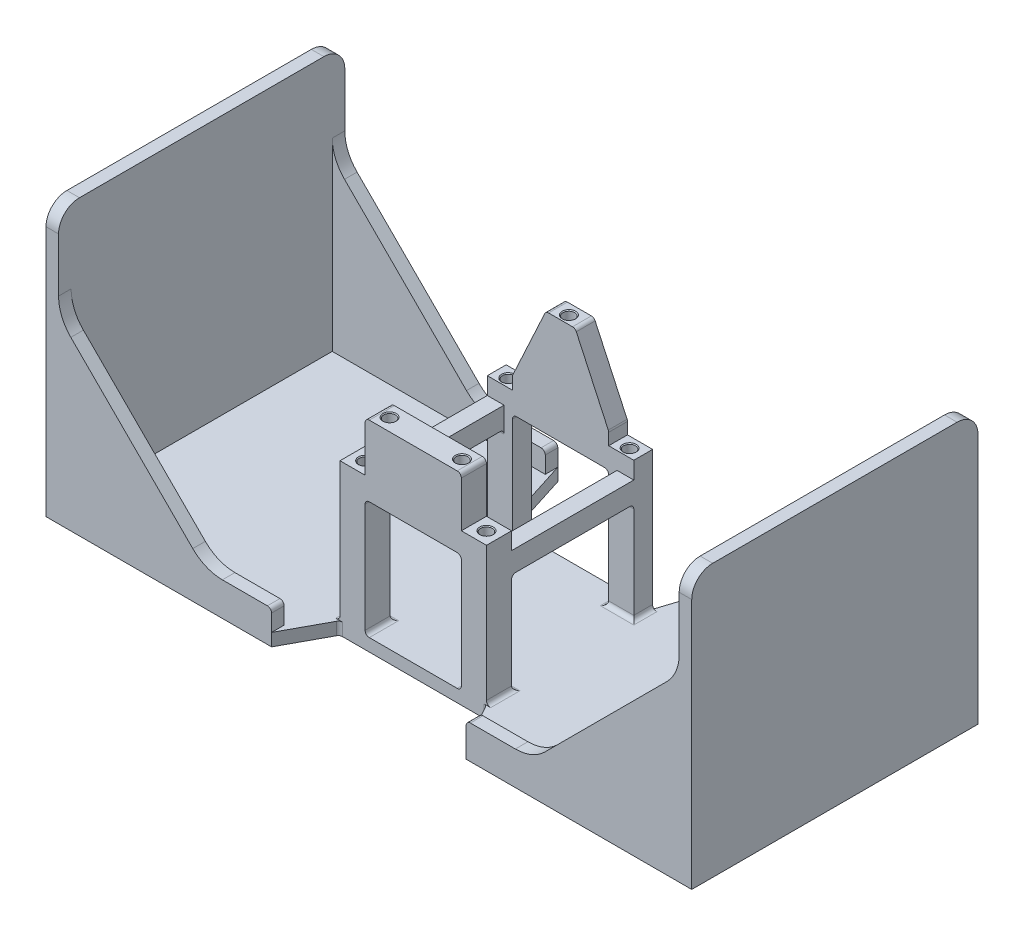
SolidWorks part; units mm, degrees
ref_plane "Front Plane" through (0, 0, 0) normal (0, 0, 1) x (1, 0, 0)
ref_plane "Top Plane" through (0, 0, 0) normal (0, 1, 0) x (1, 0, 0)
ref_plane "Right Plane" through (0, 0, 0) normal (1, 0, 0) x (0, 0, -1)
sketch "Sketch1" plane through (0, 0, 0) normal (0, 1, 0) x (1, 0, 0)
  line L1 (77.15, -34.2) -> (-77.15, -34.2)
  line L2 (77.15, -34.2) -> (77.15, 34.2)
  line L3 (77.15, 34.2) -> (-77.15, 34.2)
  line L4 (-77.15, -34.2) -> (-77.15, 34.2)
  line L5 (77.15, -34.2) -> (-77.15, 34.2) construction
  line L6 (77.15, 34.2) -> (-77.15, -34.2) construction
  point P0 (0, 0)
  dimension "D1" = 154.3
  dimension "D2" = 68.4
extrude "Boss-Extrude1" add sketch "Sketch1" along normal blind 3
sketch "Sketch2" plane through (0, 3, 0) normal (0, 1, 0) x (1, 0, 0)
  line L0 (0, 0) -> (0, -20.6) construction
  line L1 (8.65, -20.6) -> (-8.65, -20.6) construction
  line L2 (0, 0) -> (0, 13.6) construction
  line L3 (-11.5, 11.6) -> (-11.5, 16.1)
  line L8 (-11.5, -23.6) -> (11.5, -23.6)
  line L9 (-11.5, -23.6) -> (-11.5, -17.6)
  line L10 (-11.5, 16.1) -> (11.5, 16.1)
  line L11 (11.5, -23.6) -> (11.5, -17.6)
  line L12 (-11.5, -17.6) -> (11.5, -17.6)
  line L14 (-11.5, 11.6) -> (11.5, 11.6)
  line L16 (11.5, 11.6) -> (11.5, 16.1)
  line L17 (-11.5, -23.6) -> (-17.5, -23.6)
  line L18 (11.5, 16.1) -> (17.5, 16.1)
  line L19 (11.5, 16.1) -> (11.5, -23.6)
  line L20 (11.5, -23.6) -> (17.5, -23.6)
  line L21 (17.5, 16.1) -> (17.5, -23.6)
  line L22 (-17.5, 16.1) -> (-17.5, -23.6)
  line L23 (-11.5, 16.1) -> (-17.5, 16.1)
  line L24 (-11.5, 16.1) -> (-11.5, -23.6)
  circle A0 centre (-8.65, -20.6) radius 1.4
  circle A1 centre (8.65, -20.6) radius 1.4
  circle A2 centre (0, 13.6) radius 1.4
  point P5 (0, -20.6)
  point P14 (0, 16.1)
  point P15 (0, 11.6)
  point P28 (-11.5, -20.6)
  dimension "D3" = 2.8
  dimension "D4" = 2.8
  dimension "D6" = 2.8
  dimension "D1" = 20.6
  dimension "D2" = 17.3
  dimension "D5" = 13.6
  dimension "D7" = 23
  dimension "D8" = 6
  dimension "D9" = 2.5
  dimension "D10" = 6
  dimension "D12" = 2
extrude "Boss-Extrude2" add sketch "Sketch2" along normal blind 45 contours L14 L16 L10 L3 A2 | L12 L9 L8 L11 A1 A0 region at (-11.2656, 3, -13.85) region at (0, 3, 20.6)
extrude "Boss-Extrude3" add sketch "Sketch2<3>" along normal blind 8.4 from surface contours L14 L16 L10 L3 A2 region at (-11.2656, 3, -13.85) starting at face at (0, 48, -12.2)
sketch "Sketch2<3>" plane through (0, 3, 0) normal (0, 1, 0) x (1, 0, 0) same geometry as "Sketch2"
extrude "Boss-Extrude4" add sketch "Sketch2<5>" along normal blind 29 contours L24 L3 L23 L22 L17 L9 | L21 L18 L16 L19 L11 L20 region at (-14.5, 3, 3.75) region at (14.5, 3, 3.75)
sketch "Sketch2<5>" plane through (0, 3, 0) normal (0, 1, 0) x (1, 0, 0) same geometry as "Sketch2"
sketch "Sketch3" plane through (0, 32, 0) normal (0, 1, 0) x (1, 0, 0)
  line L0 (11.5, -17.6) -> (11.5, 11.6) construction
  line L1 (11.5, 11.6) -> (13.5, 11.6)
  line L2 (11.5, 11.6) -> (11.5, -17.6)
  line L3 (11.5, -17.6) -> (13.5, -17.6)
  line L4 (13.5, 11.6) -> (13.5, -17.6)
  line L6 (0, 16.1) -> (0, -23.6) construction
  line L7 (-17.5, 16.1) -> (17.5, 16.1) construction
  line L8 (-11.5, -23.6) -> (11.5, -23.6) construction
  line L9 (-11.5, -17.6) -> (-13.5, -17.6)
  line L10 (-13.5, 11.6) -> (-13.5, -17.6)
  line L11 (-11.5, 11.6) -> (-13.5, 11.6)
  line L12 (-11.5, 11.6) -> (-11.5, -17.6)
  line L14 (11.5, 11.6) -> (-11.5, 11.6) construction
  line L15 (-11.5, -17.6) -> (11.5, -17.6) construction
  dimension "D3" = 2
extrude "Cut-Extrude1" cut sketch "Sketch3" against normal up to surface (29 mm away) up to face at (0, 3, 3)
sketch "Sketch4" plane through (0, 3, 0) normal (0, 1, 0) x (1, 0, 0)
  line L0 (-77.15, -34.2) -> (77.15, -34.2) construction
  line L1 (77.15, 34.2) -> (74.15, 34.2)
  line L2 (77.15, 34.2) -> (77.15, -34.2)
  line L3 (77.15, -34.2) -> (74.15, -34.2)
  line L4 (74.15, 34.2) -> (74.15, -34.2)
  line L5 (0, -34.2) -> (0, 34.2) construction
  line L6 (-77.15, 34.2) -> (-74.15, 34.2)
  line L7 (-77.15, 34.2) -> (-77.15, -34.2)
  line L8 (-77.15, -34.2) -> (-74.15, -34.2)
  line L9 (-74.15, 34.2) -> (-74.15, -34.2)
  line L10 (74.15, 34.2) -> (23.25, 34.2)
  line L11 (74.15, 34.2) -> (74.15, 31.2)
  line L12 (74.15, 31.2) -> (23.25, 31.2)
  line L13 (23.25, 34.2) -> (23.25, 31.2)
  line L14 (77.15, 34.2) -> (-77.15, 34.2) construction
  line L15 (77.15, 0) -> (-75.15, 0) construction
  line L16 (74.15, -31.2) -> (23.25, -31.2)
  line L17 (23.25, -34.2) -> (23.25, -31.2)
  line L18 (74.15, -34.2) -> (23.25, -34.2)
  line L19 (74.15, -34.2) -> (74.15, -31.2)
  line L20 (-74.15, -31.2) -> (-23.25, -31.2)
  line L21 (-74.15, 34.2) -> (-23.25, 34.2)
  line L22 (-74.15, 34.2) -> (-74.15, 31.2)
  line L23 (-74.15, 31.2) -> (-23.25, 31.2)
  line L24 (-23.25, 34.2) -> (-23.25, 31.2)
  line L25 (-23.25, -34.2) -> (-23.25, -31.2)
  line L26 (-74.15, -34.2) -> (-23.25, -34.2)
  line L27 (-74.15, -34.2) -> (-74.15, -31.2)
  line M7 (-77.15, 34.2) -> (-77.15, -34.2)
  line M8 (-77.15, -34.2) -> (77.15, -34.2)
  line M9 (77.15, -34.2) -> (77.15, 34.2)
  line M10 (77.15, 34.2) -> (-77.15, 34.2)
  dimension "D1" = 3
  dimension "D2" = 3
  dimension "D3" = 3
  dimension "D4" = 50.9
  dimension "D5" = 50.9
  dimension "D6" = 3
extrude "Boss-Extrude5" add sketch "Sketch4" along normal blind 62 contours L4 M10 M8 M9 | L9 M10 M7 M8 region at (75.65, 3, 0) region at (-75.65, 3, 0)
extrude "Boss-Extrude6" add sketch "Sketch4<3>" along normal blind 5 contours L13 L12 L4 M10 | L17 L4 L16 M8 | L24 L9 L23 M10 | L27 L20 L25 L26 region at (48.7, 3, -32.7) region at (48.7, 3, 32.7) region at (-48.7, 3, -32.7)
sketch "Sketch4<3>" plane through (0, 3, 0) normal (0, 1, 0) x (1, 0, 0) same geometry as "Sketch4"
sketch "Sketch5" plane through (0, 3, 0) normal (0, 1, 0) x (1, 0, 0)
  line L0 (23.25, -34.2) -> (17.5, -23.6)
  line L1 (17.5, -23.6) -> (-17.5, -23.6)
  line L2 (-17.5, -23.6) -> (-23.25, -34.2)
  line L3 (-23.25, -34.2) -> (23.25, -34.2)
  line L4 (17.5, 16.1) -> (23.25, 34.2)
  line L5 (23.25, 34.2) -> (-23.25, 34.2)
  line L6 (-23.25, 34.2) -> (-17.5, 16.1)
  line L7 (-17.5, 16.1) -> (17.5, 16.1)
extrude "Cut-Extrude2" cut sketch "Sketch5" against normal through all
fillet "Fillet1" radius 5 4 edges at (-75.65, 65, 34.2) (-75.65, 65, -34.2) (75.65, 65, 34.2) (75.65, 65, -34.2)
fillet "Fillet2" radius 1 8 edges at (-17.5, 1.5, 23.6) (17.5, 1.5, 23.6) (-17.5, 1.5, -16.1) (17.5, 1.5, -16.1) (23.25, 8, 32.7) (-23.25, 8, 32.7) (-23.25, 8, -32.7) (23.25, 8, -32.7)
sketch "Sketch6" plane through (0, 32, 0) normal (0, 1, 0) x (1, 0, 0)
  line L0 (-17.5, 16.1) -> (-17.5, -23.6) construction
  line L1 (-11.5, -23.6) -> (-17.5, -23.6)
  line L2 (-11.5, -23.6) -> (-11.5, -17.6)
  line L3 (-11.5, -17.6) -> (-17.5, -17.6)
  line L4 (-17.5, -23.6) -> (-17.5, -17.6)
  line L5 (17.5, 16.1) -> (17.5, -23.6) construction
  line L6 (11.5, -23.6) -> (17.5, -23.6)
  line L7 (11.5, -23.6) -> (11.5, -17.6)
  line L8 (11.5, -17.6) -> (17.5, -17.6)
  line L9 (17.5, -23.6) -> (17.5, -17.6)
  line L10 (17.5, 13.6) -> (-17.5, 13.6) construction
  line L15 (-17.5, 16.1) -> (-17.5, -23.6) construction
  line L16 (17.5, -17.6) -> (11.5, -23.6) construction
  line L21 (17.5, -23.6) -> (11.5, -17.6) construction
  line L22 (-11.5, -17.6) -> (-17.5, -23.6) construction
  line L23 (-11.5, -23.6) -> (-17.5, -17.6) construction
  line L26 (17.5, 16.1) -> (11.5, 16.1)
  line L27 (17.5, 16.1) -> (17.5, 11.6)
  line L28 (-13.5, -17.6) -> (13.5, -17.6) construction
  line L29 (17.5, 11.6) -> (11.5, 11.6)
  line L30 (11.5, 16.1) -> (11.5, 11.6)
  line L31 (-11.5, 16.1) -> (-17.5, 16.1)
  line L32 (-11.5, 16.1) -> (-11.5, 11.6)
  line L33 (-11.5, 11.6) -> (-17.5, 11.6)
  line L34 (-17.5, 16.1) -> (-17.5, 11.6)
  circle A0 centre (14.5, -20.6) radius 1.4
  circle A1 centre (-14.5, -20.6) radius 1.4
  circle A3 centre (14.5, 13.6) radius 1.4
  circle A4 centre (0, 13.6) radius 1.4 construction
  circle A5 centre (-14.5, 13.6) radius 1.4
  point P21 (0, 13.6)
  dimension "D1" = 2.8
  dimension "D2" = 2.8
  dimension "D3" = 2.8
  dimension "D4" = 2.8
extrude "Boss-Extrude7" add sketch "Sketch6" along normal blind 4.1
sketch "Sketch8" plane through (17.5, 0, 0) normal (1, 0, 0) x (0, 0, -1)
  line L0 (-17.6, 36.1) -> (-17.6, 32) construction
  line L1 (-17.6, 27) -> (11.6, 27)
  line L2 (-17.6, 27) -> (-17.6, 3)
  line L3 (-17.6, 3) -> (11.6, 3)
  line L4 (11.6, 27) -> (11.6, 3)
  line L6 (16.1, 3) -> (-23.6, 3) construction
  line L7 (11.6, 32) -> (-17.6, 32) construction
  line L8 (11.6, 36.1) -> (11.6, 32) construction
  dimension "D1" = 5
extrude "Cut-Extrude4" cut sketch "Sketch8" against normal blind 40
sketch "Sketch9" plane through (0, 0, 23.6) normal (0, 0, 1) x (1, 0, 0)
  line L0 (11.5, 48) -> (11.5, 36.1) construction
  line L1 (-11.5, 31.1) -> (11.5, 31.1)
  line L2 (-11.5, 31.1) -> (-11.5, 3)
  line L3 (-11.5, 3) -> (11.5, 3)
  line L4 (11.5, 31.1) -> (11.5, 3)
  line L5 (-11.5, 48) -> (-11.5, 36.1) construction
  line L6 (-17.5, 3) -> (17.5, 3) construction
  line L7 (17.5, 36.1) -> (11.5, 36.1) construction
  dimension "D1" = 5
extrude "Cut-Extrude5" cut sketch "Sketch9" against normal blind 40
sketch "Sketch10" plane through (0, 0, -16.1) normal (0, 0, -1) x (-1, 0, 0)
  line L0 (0, 56.4) -> (0, 31.1) construction
  line L1 (-11.5, 56.4) -> (11.5, 56.4) construction
  line L2 (11.5, 31.1) -> (-11.5, 31.1) construction
  line L3 (3.5, 56.4) -> (-3.5, 56.4)
  line L4 (-3.5, 56.4) -> (-11.5, 39.1)
  line L5 (-11.5, 56.4) -> (-11.5, 36.1) construction
  line L6 (-11.5, 39.1) -> (-11.5, 36.1)
  line L7 (-11.5, 36.1) -> (11.5, 36.1)
  line L8 (11.5, 36.1) -> (11.5, 39.1)
  line L9 (11.5, 56.4) -> (11.5, 36.1) construction
  line L10 (11.5, 39.1) -> (3.5, 56.4)
  line L11 (-17.5, 36.1) -> (-11.5, 36.1) construction
  line L12 (11.5, 36.1) -> (17.5, 36.1) construction
  line L13 (11.5, 56.4) -> (11.5, 36.1) construction
  point P11 (0, 56.4)
  line M16 (11.5, 36.1) -> (11.5, 56.4)
  line M17 (11.5, 56.4) -> (-11.5, 56.4)
  line M18 (-11.5, 56.4) -> (-11.5, 36.1)
  dimension "D1" = 7
  dimension "D2" = 3
extrude "Cut-Extrude6" cut sketch "Sketch10" against normal up to next contours L4 M17 M18 | L10 M16 M17 region at (-8.8333, 50.6333, -16.1) region at (8.8333, 50.6333, -16.1)
fillet "Fillet3" radius 1 26 edges at (-11.5, 31.1, 20.6) (11.5, 31.1, 20.6) (17.5, 3, 20.6) (11.5, 3, 20.6) (-11.5, 3, 20.6) (-17.5, 3, 20.6) (-17.5, 3, -13.85) (17.5, 3, -13.85) (-11.5, 3, -13.85) (11.5, 3, -13.85) (-11.5, 31.1, -13.85) (11.5, 31.1, -13.85) (15.5, 27, 17.6) (-15.5, 27, 17.6) (-14.5, 3, 17.6) (14.5, 3, 17.6) (-15.5, 27, -11.6) (15.5, 27, -11.6) (-14.5, 3, -11.6) (14.5, 3, -11.6) (11.5, 39.1, -13.85) (-11.5, 39.1, -13.85) (-3.5, 56.4, -13.85) (3.5, 56.4, -13.85) (11.5, 48, 20.6) (-11.5, 48, 20.6)
chamfer "Chamfer1" distance 0.2 angle 45 14 edges at (-14.5, 32, -12.2) (-14.5, 36.1, -12.2) (0, 56.4, -12.2) (0, 31.1, -12.2) (14.5, 32, -12.2) (14.5, 36.1, -12.2) (8.65, 48, 22) (8.65, 31.1, 22) (-8.65, 48, 22) (-8.65, 31.1, 22) (-14.5, 32, 22) (-14.5, 36.1, 22) (14.5, 32, 22) (14.5, 36.1, 22)
chamfer "Chamfer2" distance 35 angle 45 4 edges at (74.15, 8, -32.7) (74.15, 8, 32.7) (-74.15, 8, -32.7) (-74.15, 8, 32.7)
fillet "Fillet4" radius 10 8 edges at (74.15, 43, -32.7) (74.15, 43, 32.7) (-74.15, 43, -32.7) (-74.15, 43, 32.7) (39.15, 8, 32.7) (39.15, 8, -32.7) (-39.15, 8, -32.7) (-39.15, 8, 32.7)
